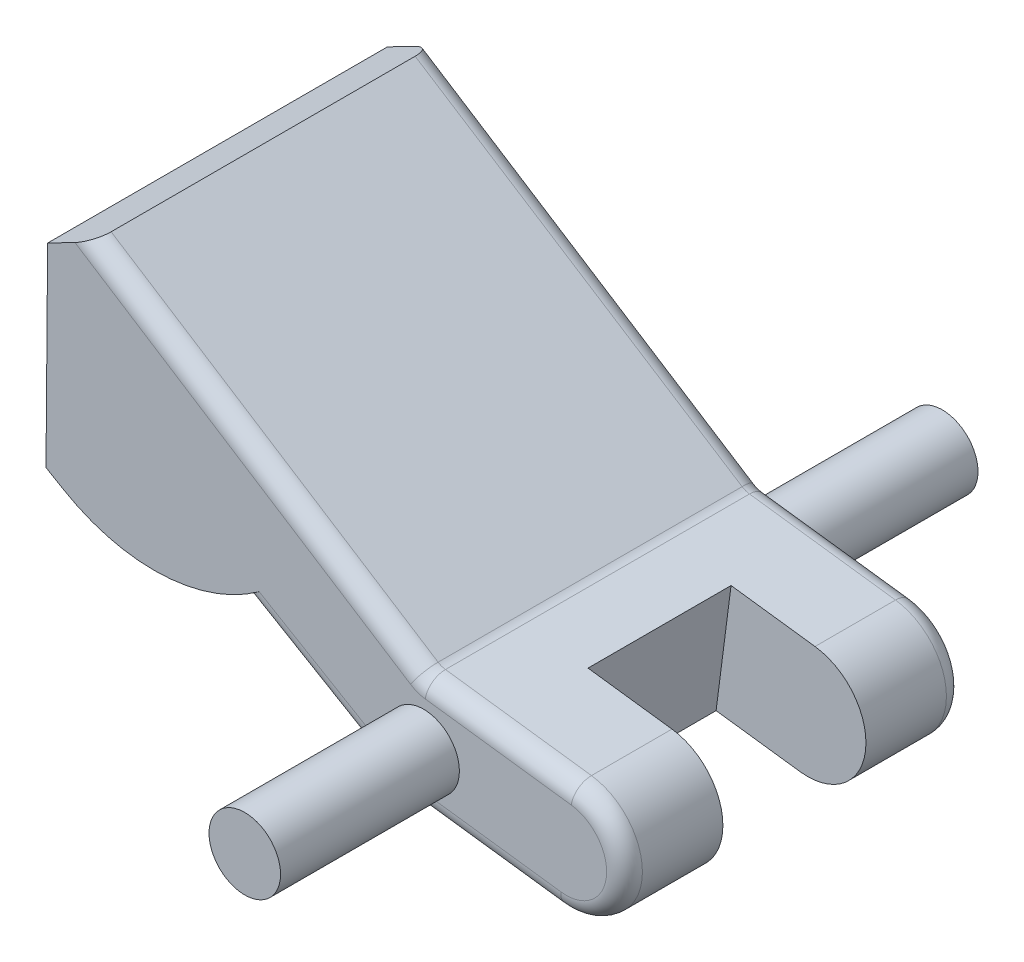
SolidWorks part; units mm, degrees
ref_plane "Front Plane" through (0, 0, 0) normal (0, 0, 1) x (1, 0, 0)
ref_plane "Top Plane" through (0, 0, 0) normal (0, 1, 0) x (1, 0, 0)
ref_plane "Right Plane" through (0, 0, 0) normal (1, 0, 0) x (0, 0, -1)
sketch "Sketch1" plane through (0, 0, 0) normal (0, 0, 1) x (1, 0, 0)
  line L0 (0, 3.5617) -> (-21, 17)
  line L2 (-1.5216, -2.5855) -> (-10.1399, 2.4865)
  line L4 (-10.1399, 2.4865) -> (-12.6759, -1.8227)
  line L5 (-12.6759, -1.8227) -> (-21.1154, 3.1441)
  line L6 (-21.1154, 3.1441) -> (-21, 17)
  line L7 (-0.3843, -2.9753) -> (7.5498, -4)
  line L8 (0, 3.5617) -> (8.3866, 2.4785)
  line L9 (-13.9572, -4) -> (8.3866, -4) construction
  arc A0 (-0.3843, -2.9753) -> (-1.5216, -2.5855) centre (0, 0) cw
  arc A1 (8.3866, 2.4785) -> (7.5498, -4) centre (7.9682, -0.7607) cw
  point P14 (0, 0)
  point P15 (0, 0)
  point P16 (8.544, 0)
  point P17 (7.5207, 2.7287)
  point P18 (7.5207, 2.7287)
  point P19 (-25.0337, 23.5654)
  point P20 (7.5514, -3.9971)
  point P21 (7.1547, -4.6702)
  point P22 (0, 0)
  point P23 (6.9769, -5)
  point P24 (22.5866, -5)
  dimension "D1" = 3
  dimension "D2" = 10
  dimension "D3" = 5
  dimension "D4" = 21
  dimension "D5" = 120
  dimension "D6" = 12
  dimension "D7" = 8
  dimension "D8" = 4
  dimension "D9" = 21
extrude "Boss-Extrude1" add sketch "Sketch1" along normal mid plane 19
sketch "Sketch2" plane through (0, 0, 0) normal (0, 0, 1) x (1, 0, 0)
  circle A0 centre (0, 0) radius 2
  dimension "D1" = 4
extrude "Boss-Extrude2" add sketch "Sketch2" along normal mid plane 39
sketch "Sketch6" plane through (0, 0, 0) normal (0, 0, 1) x (1, 0, 0)
  line L0 (0, 0) -> (-17.4384, 4.4611) construction
  line L1 (-21.1154, 3.1441) -> (-12.6759, -1.8227) construction
  circle A0 centre (-17.4384, 4.4611) radius 1
  dimension "D2" = 2
  dimension "D1" = 18
  dimension "D3" = 3
extrude "Boss-Extrude3" [suppressed] add sketch "Sketch6" along normal mid plane 30 separate body
sketch "Sketch7" plane through (-8.6183, 5.072, 0) normal (0.8618, -0.5072, 0) x (0, 0, -1)
  line L0 (-9.5, -8) -> (9.5, -8) construction
  line L1 (-5, -8) -> (5, -8)
  line L2 (-5, -8) -> (-5, -3)
  line L3 (-5, -3) -> (5, -3)
  line L4 (5, -8) -> (5, -3)
  line L5 (-9.5, -3) -> (9.5, -3) construction
  line L6 (0, -8) -> (0, -3) construction
  dimension "D1" = 10
extrude "Cut-Extrude3" cut sketch "Sketch7" against normal through all
sketch "Sketch5" plane through (-1.5216, -2.5855, 0) normal (-0.5072, -0.8618, 0) x (0.8618, -0.5072, 0)
  line L0 (-22.6793, 0) -> (0, 0) construction
  line L1 (-22.6793, -5) -> (-22.6793, 5) construction
  circle A0 centre (-16.27, 0) radius 2.413
  circle A1 centre (-16.27, 0) radius 3.302
  dimension "D1" = 6.604
  dimension "D2" = 4.826
  dimension "D3" = 16.27
extrude "Cut-Extrude2" cut sketch "Sketch5" against normal blind 3.5
sketch "Sketch8" plane through (-1.5216, -2.5855, 0) normal (-0.5072, -0.8618, 0) x (0.8618, -0.5072, 0)
  line L1 (-19.7926, -5) -> (-10, -5)
  line L2 (-19.7926, -5) -> (-19.7926, 5)
  line L3 (-19.7926, 5) -> (-10, 5)
  line L4 (-10, -5) -> (-10, 5)
extrude "Cut-Extrude4" [suppressed] cut sketch "Sketch8" along normal up to surface (5 mm away)
fillet "Fillet3" radius 10 2 edges at (-12.6759, -1.8227, -7.25) (-12.6759, -1.8227, 7.25)
fillet "Fillet1" radius 1 2 edges at (-12.6978, 3.9918, 0) (-13.464, 4.4427, 0)
fillet "Fillet2" radius 1 13 edges at (-5.8307, -0.0495, 9.5) (-5.8307, -0.0495, -9.5) (-0.9727, -2.8379, 9.5) (-0.9727, -2.8379, -9.5) (3.5828, -3.4876, 9.5) (3.5828, -3.4876, -9.5) (11.2075, -1.1791, 9.5) (11.2075, -1.1791, -9.5) (4.1933, 3.0201, 9.5) (4.1933, 3.0201, -9.5) (0, 3.5617, 0) (-10.5, 10.2808, 9.5) (-10.5, 10.2808, -9.5)
sketch "Sketch9" plane through (0.4525, 3.5032, 0) normal (0.1281, 0.9918, 0) x (0.9918, -0.1281, 0)
  line L0 (3.2662, 0) -> (11.2662, 0) construction
  line L1 (3.2662, -4) -> (11.2662, -4)
  line L2 (3.2662, -4) -> (3.2662, 4)
  line L3 (3.2662, 4) -> (11.2662, 4)
  line L4 (11.2662, -4) -> (11.2662, 4)
  line L5 (11.2662, -8.5) -> (11.2662, 8.5) construction
  dimension "D1" = 8
  dimension "D2" = 8
extrude "Cut-Extrude5" cut sketch "Sketch9" against normal up to surface (6.5323 mm away) up to face at (3.5828, -3.4876, 0)
chamfer "Chamfer1" distance 3 angle 60 5 edges at (-21.0626, 9.4816, 9.5) (-21.0626, 9.4816, -9.5) (-21.0029, 16.6541, 9.2071) (-21.0029, 16.6541, -9.2071) (-21, 17, 0)
